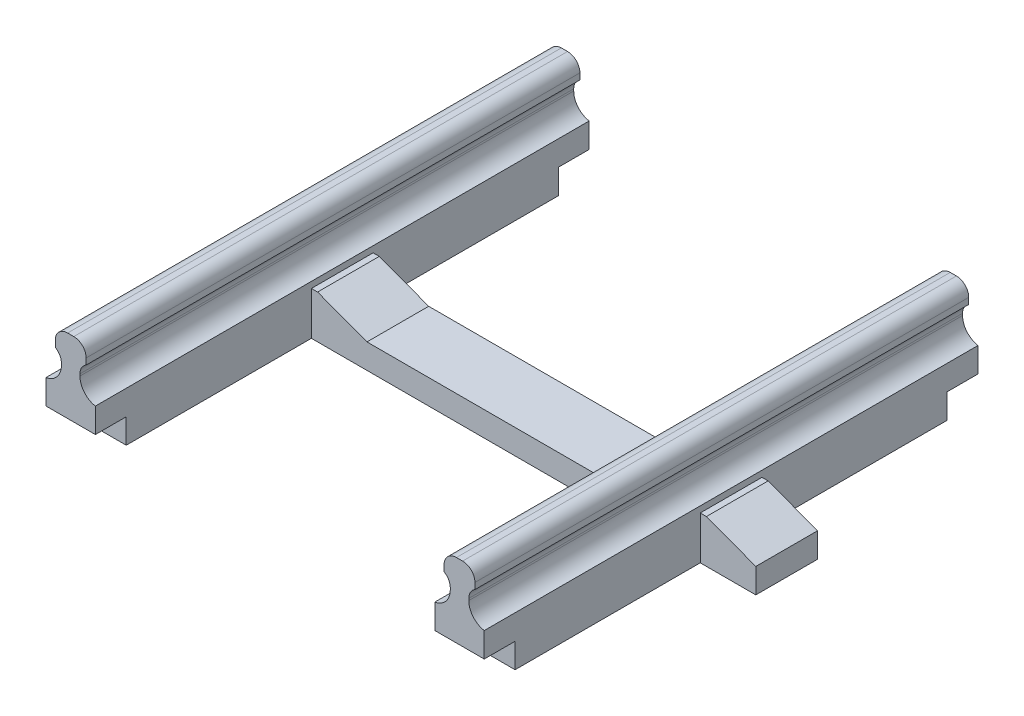
SolidWorks part; units mm, degrees
other "标注1"
sketch "草图3" plane through (-22.25, 4, -10) normal (-0.231, 0.6469, -0.7268) x (-0.9696, -0.2151, 0.1167)
other "标注2"
sketch "草图4" plane through (22.25, 8, -30) normal (0.0083, 0.0567, -0.9984) x (-0.9991, 0.0415, -0.0059)
ref_plane "前视基准面" through (0, 0, 0) normal (0, 0, 1) x (1, 0, 0)
ref_plane "上视基准面" through (0, 0, 0) normal (0, 1, 0) x (1, 0, 0)
ref_plane "右视基准面" through (0, 0, 0) normal (1, 0, 0) x (0, 0, -1)
other "Configuration Table"
sketch "草图1" plane through (0, 0, 0) normal (0, 1, 0) x (1, 0, 0)
  line L0 (-13.75, 11.25) -> (-13.75, -11.25)
  line L13 (-17.75, -11.25) -> (17.75, -11.25)
  line L21 (-17.75, -11.25) -> (-17.75, 11.25)
  line L22 (-17.75, 11.25) -> (17.75, 11.25)
  line L23 (17.75, -11.25) -> (17.75, 11.25)
  line L24 (-17.75, -11.25) -> (17.75, 11.25) construction
  line L25 (-17.75, 11.25) -> (17.75, -11.25) construction
  line L27 (13.75, 11.25) -> (13.75, -11.25)
  line L29 (-13.75, 0) -> (13.75, 0) construction
  line L32 (-22.25, 11.25) -> (22.25, 11.25)
  line L33 (-22.25, 11.25) -> (-22.25, 6.25)
  line L34 (-22.25, 6.25) -> (22.25, 6.25)
  line L35 (22.25, 11.25) -> (22.25, 6.25)
  point P0 (0, 0)
  point P15 (0, 6.25)
  dimension "D3" = 27.5
  dimension "D4" = 5
  dimension "D1" = 35.5
  dimension "D2" = 22.5
  dimension "D5" = 44.5
extrude "凸台-拉伸1" add sketch "草图1" along normal blind 4 contours L34 L21 L13 L0 | L34 L27 L13 L23 | L27 L34 L23 L22 | L21 L34 L0 L22 region at (-15.75, 0, -8.75) region at (-15.75, 0, 2.5) region at (15.75, 0, -8.75) region at (15.75, 0, 2.5)
extrude "凸台-拉伸2" add sketch "草图1<7>" along normal blind 3.5 contours L34 L35 L32 L33
sketch "草图1<7>" plane through (0, 0, 0) normal (0, 1, 0) x (1, 0, 0) same geometry as "草图1"
sketch "草图2" plane through (0, 0, -11.25) normal (0, 0, -1) x (-1, 0, 0)
  line L0 (18.25, 3.5) -> (22.25, 2)
  line L1 (22.25, 3.5) -> (18.25, 3.5)
  line L2 (22.25, 3.5) -> (22.25, 2)
  line L3 (22.25, 2) -> (18.25, 2) construction
  line L4 (18.25, 3.5) -> (18.25, 2) construction
  line L5 (-22.25, 2) -> (-18.25, 3.5)
  line L6 (-22.25, 3.5) -> (-18.25, 3.5)
  line L7 (-22.25, 3.5) -> (-22.25, 2)
  line L8 (-22.25, 2) -> (-18.25, 2) construction
  line L9 (-18.25, 3.5) -> (-18.25, 2) construction
  line L10 (13.75, 3.5) -> (-13.75, 3.5) construction
  line L11 (-13.25, 3.5) -> (-9.25, 3.5)
  line L12 (-13.25, 3.5) -> (-13.25, 2) construction
  line L13 (-13.25, 2) -> (-9.25, 2) construction
  line L14 (-9.25, 3.5) -> (-9.25, 2)
  line L15 (-13.75, 3.5) -> (-13.25, 3.5) construction
  line L16 (13.25, 3.5) -> (9.25, 3.5)
  line L17 (13.25, 3.5) -> (13.25, 2) construction
  line L18 (13.25, 2) -> (9.25, 2) construction
  line L19 (9.25, 3.5) -> (9.25, 2)
  line L20 (13.25, 3.5) -> (13.75, 3.5) construction
  line L21 (17.75, 3.5) -> (18.25, 3.5) construction
  line L22 (-13.25, 3.5) -> (-9.25, 2)
  line L23 (9.25, 2) -> (13.25, 3.5)
  line L24 (-9.25, 2) -> (9.25, 2)
  line L25 (-9.25, 3.5) -> (9.25, 3.5)
  line L26 (-15.75, 4) -> (-15.75, 6.5) construction
  line L27 (14.5, 8) -> (17, 8)
  line L28 (14.5, 8) -> (14.5, 6.5)
  line L29 (14.5, 6.5) -> (17, 6.5)
  line L30 (17, 8) -> (17, 6.5)
  line L31 (-17, 8) -> (-14.5, 8)
  line L32 (-17, 8) -> (-17, 6.5)
  line L33 (-17, 6.5) -> (-14.5, 6.5)
  line L34 (-14.5, 8) -> (-14.5, 6.5)
  line L35 (-13.75, 4) -> (-17.75, 4) construction
  line L36 (15.75, 6.5) -> (15.75, 4) construction
  line L37 (17.75, 4) -> (13.75, 4) construction
  line L38 (15, 6.5) -> (15, 4)
  line L39 (16.5, 6.5) -> (16.5, 4)
  line L40 (16.5, 4) -> (15.75, 4)
  line L41 (15.75, 4) -> (15, 4)
  line L42 (-16.5, 6.5) -> (-16.5, 4)
  line L43 (-16.5, 4) -> (-15.75, 4)
  line L44 (-15.75, 4) -> (-15, 4)
  line L45 (-15, 4) -> (-15, 6.5)
  line M9 (22.25, 3.5) -> (17.75, 3.5)
  line M11 (17.75, 4) -> (13.75, 4)
  line M13 (13.75, 3.5) -> (-13.75, 3.5)
  line M15 (-13.75, 4) -> (-17.75, 4)
  line M17 (-17.75, 3.5) -> (-22.25, 3.5)
  line M18 (-22.25, 3.5) -> (-22.25, 0)
  line M20 (22.25, 0) -> (22.25, 3.5)
  dimension "D1" = 4
  dimension "D2" = 1.5
  dimension "D3" = 2.5
  dimension "D4" = 1.5
  dimension "D5" = 2.5
  dimension "D6" = 1.5
extrude "切除-拉伸1" cut sketch "草图2" against normal through all contours L14 L24 L19 M13 | L19 L23 M13 | L22 L14 M13 | L5 M18 M17 | L0 M9 M20 region at (-20.9167, 3, -11.25) region at (20.9167, 3, -11.25) region at (10.5833, 3, -11.25) region at (0, 2.75, -11.25) region at (-10.5833, 3, -11.25)
extrude "凸台-拉伸4" add sketch "草图2<3>" against normal through all contours L34 L31 L32 L33 | L45 L33 L42 M15 | L30 L27 L28 L29 | L39 L29 L38 M11 region at (-15.75, 7.25, -11.25) region at (-15.75, 5.25, -11.25) region at (15.75, 7.25, -11.25) region at (15.75, 5.25, -11.25)
sketch "草图2<3>" plane through (0, 0, -11.25) normal (0, 0, -1) x (-1, 0, 0) same geometry as "草图2"
fillet "圆角1" radius 1 4 edges at (-16.5, 6.5, 0) (-15, 6.5, 0) (15, 6.5, 0) (16.5, 6.5, 0)
fillet "圆角2" radius 1.5 4 edges at (16.5, 4, 0) (15, 4, 0) (-15, 4, 0) (-16.5, 4, 0)
fillet "圆角3" radius 1 4 edges at (-17, 8, 0) (14.5, 8, 0) (17, 8, 0) (-14.5, 8, 0)
sketch "草图5" plane through (17.75, 0, 0) normal (1, 0, 0) x (0, 0, -1)
  line L0 (-11.25, 4) -> (-11.25, 0) construction
  line L1 (-11.25, 2) -> (-8.75, 2)
  line L2 (-11.25, 2) -> (-11.25, 0)
  line L3 (-11.25, 0) -> (-8.75, 0)
  line L4 (-8.75, 2) -> (-8.75, 0)
  line L5 (-11.25, 0) -> (6.25, 0) construction
  dimension "D1" = 2.5
  dimension "D2" = 2
extrude "切除-拉伸2" cut sketch "草图5" against normal through all
sketch "草图10" plane through (0, 2, 0) normal (0, -1, 0) x (1, 0, 0)
  line L0 (13.75, 11.25) -> (17.75, 8.75) construction
  line L1 (13.75, 11.25) -> (17.75, 11.25) construction
  line L2 (13.75, 8.75) -> (13.75, 11.25) construction
  line L3 (13.75, 8.75) -> (17.75, 8.75) construction
  line L4 (17.75, 8.75) -> (17.75, 11.25) construction
  line L5 (-17.75, 11.25) -> (-13.75, 8.75) construction
  line L6 (-17.75, 11.25) -> (-17.75, 8.75) construction
  line L7 (-17.75, 11.25) -> (-13.75, 11.25) construction
  line L8 (-13.75, -6.25) -> (-13.75, 8.75) construction
  line L9 (-17.75, 8.75) -> (-13.75, 8.75) construction
  circle A0 centre (15.75, 10) radius 0.4
  circle A1 centre (-15.75, 10) radius 0.4
  dimension "D1" = 0.8
extrude "切除-拉伸3" cut sketch "草图10" against normal blind 2
sketch "草图8" plane through (22.25, 0, 0) normal (1, 0, 0) x (0, 0, -1)
  line L0 (8.75, 0) -> (8.75, 18.5305)
  line L1 (11.25, 0) -> (6.25, 0) construction
ref_plane "基准面1" through (0, 0, -8.75) normal (0, 0, -1) x (-1, 0, 0)
mirror "镜向1" about plane through (0, 0, -8.75) normal (0, 0, -1) of bodies 202 196
